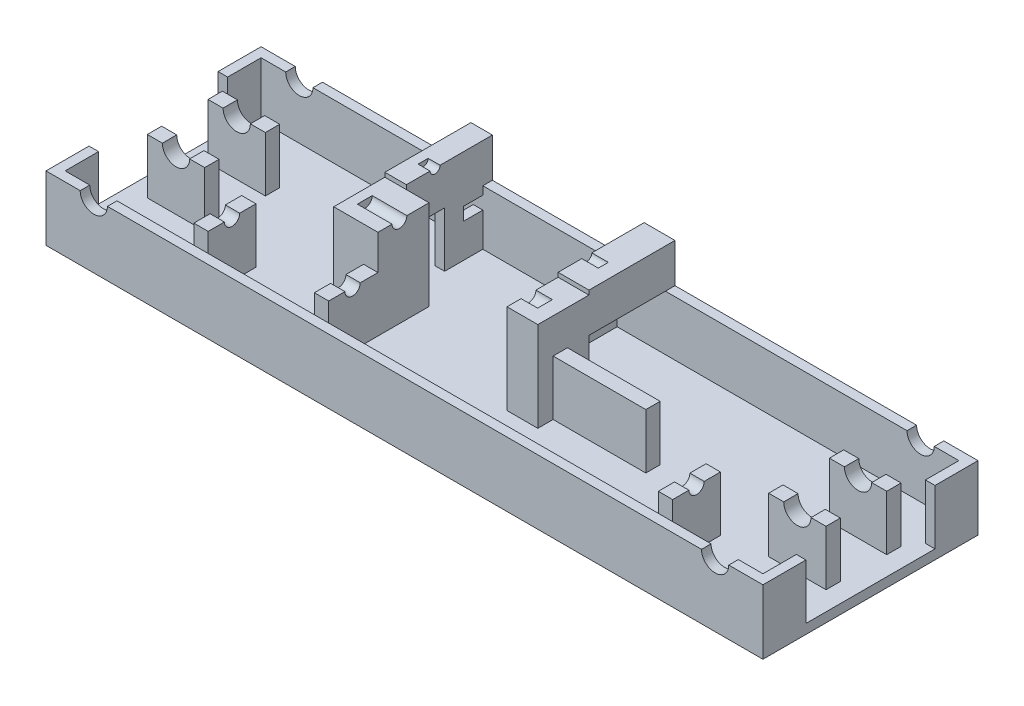
SolidWorks part; units mm, degrees
ref_plane "前视基准面" through (0, 0, 0) normal (0, 0, 1) x (1, 0, 0)
ref_plane "上视基准面" through (0, 0, 0) normal (0, 1, 0) x (1, 0, 0)
ref_plane "右视基准面" through (0, 0, 0) normal (1, 0, 0) x (0, 0, -1)
other "Configuration Table"
sketch "草图1" plane through (0, 0, 0) normal (0, 1, 0) x (1, 0, 0)
  line L1 (-75, -22.5) -> (75, -22.5)
  line L2 (-75, -22.5) -> (-75, 22.5)
  line L3 (-75, 22.5) -> (75, 22.5)
  line L4 (75, -22.5) -> (75, 22.5)
  line L5 (-75, -22.5) -> (75, 22.5) construction
  line L6 (-75, 22.5) -> (75, -22.5) construction
  point P0 (0, 0)
  dimension "D1" = 150
  dimension "D2" = 45
extrude "凸台-拉伸1" add sketch "草图1" along normal blind 2
sketch "草图2" plane through (0, 2, 0) normal (0, 1, 0) x (1, 0, 0)
  line L0 (-75, 22.5) -> (75, 22.5)
  line L1 (75, 22.5) -> (75, 13.5)
  line L2 (75, -22.5) -> (75, 22.5) construction
  line L3 (75, -22.5) -> (-75, -22.5)
  line L4 (-75, -22.5) -> (-75, -13.5)
  line L5 (-73, 20.5) -> (-28.6, 20.5)
  line L6 (73, 20.5) -> (73, 13.5)
  line L7 (73, -20.5) -> (-73, -20.5)
  line L8 (-73, -20.5) -> (-73, -13.5)
  line L9 (1.5, 20.5) -> (73, 20.5)
  line L23 (-1, 20.5) -> (-1, 12.5)
  line L24 (-73, 13.5) -> (-75, 13.5)
  line L25 (-75, -13.5) -> (-73, -13.5)
  line L26 (75, 13.5) -> (73, 13.5)
  line L27 (75, -13.5) -> (73, -13.5)
  line L28 (-75, 13.5) -> (-75, 22.5)
  line L29 (-73, 13.5) -> (-73, 20.5)
  line L30 (73, -13.5) -> (73, -20.5)
  line L31 (75, -13.5) -> (75, -22.5)
  line L32 (-1, 12.5) -> (1.5, 12.5)
  line L33 (-71, -2.3) -> (-59, -2.3)
  line L34 (-71, -2.3) -> (-71, -5.3)
  line L35 (-71, -5.3) -> (-59, -5.3)
  line L36 (-59, -2.3) -> (-59, -5.3)
  line L37 (-75, 22.5) -> (-75, -22.5) construction
  line L38 (59, -2.3) -> (71, -2.3)
  line L39 (59, -2.3) -> (59, -5.3)
  line L40 (59, -5.3) -> (71, -5.3)
  line L41 (71, -2.3) -> (71, -5.3)
  line L42 (75, -22.5) -> (75, 22.5) construction
  line L43 (-55, -5.4) -> (-75, -5.4) construction
  line L44 (75, -5.4) -> (55, -5.4) construction
  line L45 (66.4142, 10.5) -> (67.4958, 10.5) construction
  line L46 (-71, 10.4) -> (-59, 10.4)
  line L47 (-71, 10.4) -> (-71, 7.4)
  line L48 (-71, 7.4) -> (-59, 7.4)
  line L49 (-59, 10.4) -> (-59, 7.4)
  line L50 (59, 10.4) -> (71, 10.4)
  line L51 (59, 10.4) -> (59, 7.4)
  line L52 (59, 7.4) -> (71, 7.4)
  line L53 (71, 10.4) -> (71, 7.4)
  line L54 (-63.5858, 10.5) -> (-62.5042, 10.5) construction
  line L55 (1.5, 20.5) -> (1.5, 12.5)
  line L57 (-28.6, 20.5) -> (-28.6, 12.5)
  line L58 (-28.6, 12.5) -> (-26.6, 12.5)
  line L59 (-26.6, 20.5) -> (-26.6, 12.5)
  line L60 (-26.6, 20.5) -> (-1, 20.5)
  point P57 (-26.6, 16.5)
  dimension "D1" = 2
  dimension "D2" = 2
  dimension "D3" = 2
  dimension "D4" = 2
  dimension "D5" = 9
  dimension "D6" = 3
  dimension "D7" = 3
  dimension "D8" = 12
  dimension "D9" = 12
  dimension "D10" = 4
  dimension "D11" = 4
  dimension "D12" = 0.1
  dimension "D13" = 0.1
  dimension "D14" = 0.1
  dimension "D15" = 0.1
  dimension "D16" = 3
  dimension "D17" = 2.5
  dimension "D18" = 2
  dimension "D19" = 71.5
  dimension "D20" = 8
  dimension "D21" = 48.4
extrude "凸台-拉伸2" add sketch "草图2" along normal up to surface (11.5 mm away)
sketch "草图4" plane through (0, 2, 0) normal (0, 1, 0) x (1, 0, 0)
  line L1 (-50.0747, -6.5) -> (-47.0747, -6.5)
  line L2 (-50.0747, -6.5) -> (-50.0747, -16.5)
  line L3 (-50.0747, -16.5) -> (-47.0747, -16.5)
  line L4 (-47.0747, -6.5) -> (-47.0747, -16.5)
  line L5 (-31.1, 4.5) -> (-21.85, 4.5)
  line L6 (-31.1, 4.5) -> (-31.1, -6.2)
  line L7 (-24.85, -16.5) -> (-21.85, -16.5)
  line L8 (-21.85, 4.5) -> (-21.85, -16.5)
  line L9 (47.1147, -6.5) -> (50.1147, -6.5)
  line L10 (47.1147, -6.5) -> (47.1147, -16.5)
  line L11 (47.1147, -16.5) -> (50.1147, -16.5)
  line L12 (50.1147, -6.5) -> (50.1147, -16.5)
  line L13 (5.15, 4.5) -> (11.6, 4.5)
  line L14 (5.15, 4.5) -> (5.15, -6.2)
  line L15 (5.15, -6.2) -> (11.6, -6.2)
  line L16 (11.6, 4.5) -> (11.6, 0)
  line L26 (31, 0) -> (11.6, 0)
  line L28 (11.6, -3) -> (31, -3)
  line L31 (-50.2747, -15.25) -> (-50.2747, -7.75) construction
  line L32 (50.3147, -7.75) -> (50.3147, -15.25) construction
  line L33 (-29.7348, -10) -> (-29.7348, -13) construction
  line L34 (56.24, -10) -> (-56.2, -10) construction
  line L35 (-56.2, -13) -> (56.24, -13) construction
  line L36 (-29.7348, -11.5) -> (-37.5732, -11.5) construction
  line L37 (-21.55, -10.8234) -> (-21.55, -11.245) construction
  line L38 (31, 0) -> (31, -3)
  line L40 (11.6, -3) -> (11.6, -6.2)
  line L41 (75, -13.5) -> (75, 13.5) construction
  line L42 (-26.35, -3.2) -> (7.05, -3.2) construction
  line L43 (-31.1, -6.2) -> (-24.85, -6.2)
  line L44 (-24.85, -6.2) -> (-24.85, -16.5)
  line L45 (11.7, 3.8856) -> (11.7, 17.1144) construction
  line L46 (5.05, 2.196) -> (5.05, 3.4405) construction
  line L47 (-75, 13.5) -> (-75, -13.5) construction
  line L48 (-73, 20.5) -> (-28.6, 20.5) construction
  dimension "D1" = 3
  dimension "D2" = 43.9
  dimension "D3" = 3
  dimension "D4" = 10
  dimension "D5" = 0.2
  dimension "D6" = 0.2
  dimension "D7" = 0.3
  dimension "D8" = 16
  dimension "D9" = 44
  dimension "D10" = 3
  dimension "D11" = 3
  dimension "D12" = 0.1
  dimension "D13" = 3
  dimension "D14" = 0.1
extrude "凸台-拉伸3" add sketch "草图4" along normal up to surface (11.5 mm away) up to face at (-6.8375, 13.5, -17)
sketch "草图5" plane through (0, 0, 22.5) normal (0, 0, 1) x (1, 0, 0)
  circle A0 centre (-65, 13.5) radius 2.85
  arc A1 (-63.05, 11.5609) -> (-63.05, 15.4391) centre (-65, 13.5) ccw construction
  circle A2 centre (65, 13.5) radius 2.85
  arc A3 (66.95, 11.5609) -> (66.95, 15.4391) centre (65, 13.5) ccw construction
  dimension "D1" = 0.1
  dimension "D2" = 0.1
extrude "切除-拉伸1" cut sketch "草图5" against normal up to surface (45 mm away) up to face at (0, 6.75, -22.5)
sketch "草图6" plane through (50.1147, 0, 0) normal (1, 0, 0) x (0, 0, -1)
  line L0 (-16.5, 13.5) -> (-6.5, 13.5) construction
  circle A0 centre (-11.5, 13.5) radius 1.6
  circle A1 centre (-11.5, 13.5) radius 1.5 construction
  dimension "D1" = 0.1
extrude "切除-拉伸2" cut sketch "草图6" against normal up to surface (125.1147 mm away) up to face at (-75, 7.25, 0)
sketch "草图7" plane through (0, 13.5, 0) normal (0, 1, 0) x (1, 0, 0)
  line L0 (5.15, 22.5) -> (5.15, -6.2)
  line L3 (5.15, 22.5) -> (11.6, 22.5)
  line L4 (11.6, -6.2) -> (11.6, 22.5)
  line L5 (-26.6, 22.5) -> (-26.6, 4.5)
  line L6 (-26.6, 4.5) -> (-21.85, 4.5)
  line L7 (-21.85, 4.5) -> (-21.85, -6.2)
  line L8 (-21.85, -9.9) -> (-21.85, 4.5) construction
  line L9 (-21.85, -6.2) -> (-31.1, -6.2)
  line L10 (-31.1, -6.2) -> (-31.1, 22.5)
  line L11 (-31.1, 22.5) -> (-26.6, 22.5)
  line L12 (-21.85, 4.5) -> (-31.1, 4.5) construction
  line L13 (62.15, 22.5) -> (-62.15, 22.5) construction
  line L14 (5.15, -6.2) -> (11.6, -6.2)
  line L15 (-75, 22.5) -> (-75, 13.5) construction
  line L17 (11.6, -6.2) -> (11.6, -3) construction
  dimension "D2" = 48.4
  dimension "D3" = 4.5
extrude "凸台-拉伸6" add sketch "草图7" along normal up to surface (7.3 mm away)
sketch "草图8" plane through (0, 20.8, 0) normal (0, 1, 0) x (1, 0, 0)
  line L1 (-31.1, 22.5) -> (-26.6, 22.5)
  line L2 (-31.1, 22.5) -> (-31.1, 4.5)
  line L3 (-31.1, 4.5) -> (-26.6, 4.5)
  line L4 (-26.6, 22.5) -> (-26.6, 4.5)
  line L5 (5.15, 22.5) -> (11.6, 22.5)
  line L6 (5.15, 22.5) -> (5.15, 4.5)
  line L7 (5.15, 4.5) -> (11.6, 4.5)
  line L8 (11.6, 22.5) -> (11.6, 4.5)
extrude "凸台-拉伸7" add sketch "草图8" along normal up to surface (0.9 mm away)
sketch "草图9" plane through (11.6, 0, 0) normal (1, 0, 0) x (0, 0, -1)
  circle A0 centre (10.5, 21.7) radius 1.05
  circle A1 centre (-1.7, 20.8) radius 1.55
  circle A2 centre (10.5, 21.7) radius 1 construction
  circle A3 centre (-1.7, 20.8) radius 1.5 construction
  dimension "D1" = 0.05
  dimension "D2" = 0.05
extrude "切除-拉伸3" cut sketch "草图9" against normal offset from surface (37.7 mm away) 2 from offset 3 up to face at (-31.1, 14.3889, -7.9) offset against normal yes
sketch "草图10" plane through (1.5, 0, 0) normal (1, 0, 0) x (0, 0, -1)
  line L0 (20.5, 13.5) -> (20.5, 2) construction
  line L1 (16.5, 11.8) -> (20.5, 11.8)
  line L2 (16.5, 11.8) -> (16.5, 9.1)
  line L3 (16.5, 9.1) -> (20.5, 9.1)
  line L4 (20.5, 11.8) -> (20.5, 9.1)
  line L6 (16.6, 11.7) -> (20.4, 11.7) construction
  line L7 (16.6, 9.2) -> (20.4, 9.2) construction
  line L8 (16.6, 11.7) -> (16.6, 9.2) construction
  dimension "D1" = 0.1
  dimension "D2" = 0.1
  dimension "D3" = 0.1
extrude "切除-拉伸4" cut sketch "草图10" against normal up to surface (30.1 mm away) up to face at (-28.6, 7.75, -16.5)
